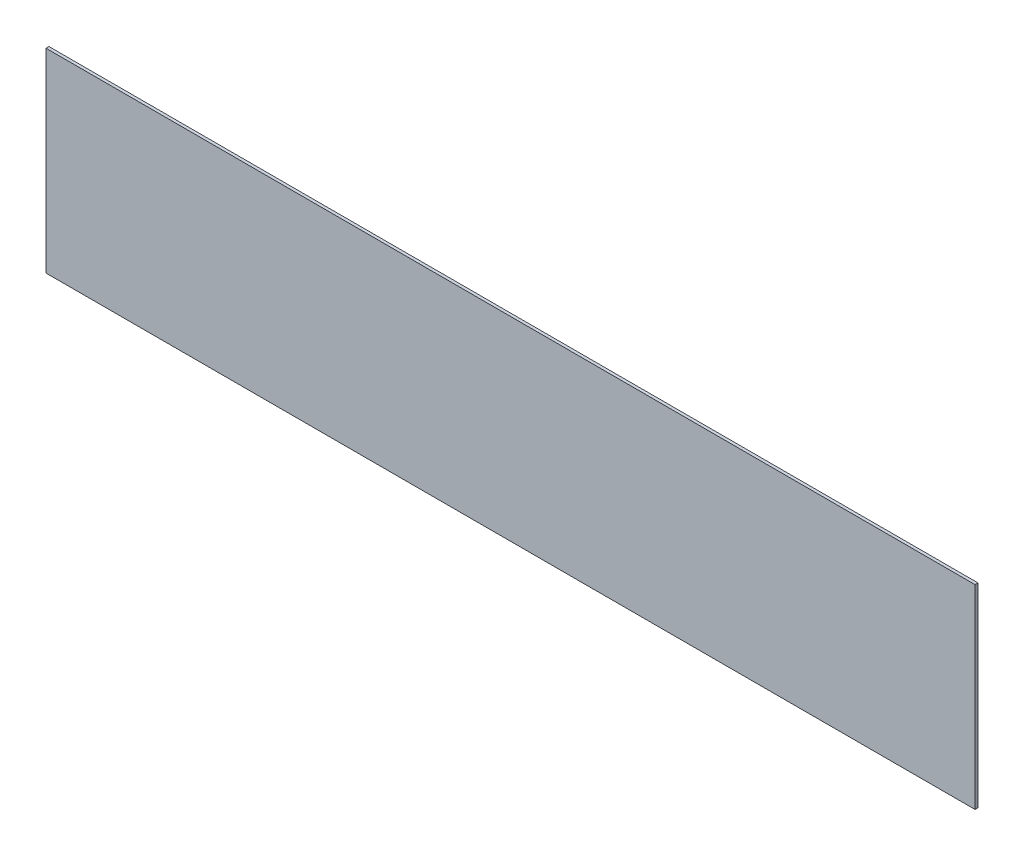
SolidWorks part; units mm, degrees
material "Pine"
ref_plane "Front Plane" through (0, 0, 0) normal (0, 0, 1) x (1, 0, 0)
ref_plane "Top Plane" through (0, 0, 0) normal (0, 1, 0) x (1, 0, 0)
ref_plane "Right Plane" through (0, 0, 0) normal (1, 0, 0) x (0, 0, -1)
sketch "Sketch2" plane through (0, 0, 0) normal (0, 0, 1) x (1, 0, 0)
  line L1 (0, 0) -> (1003.3, 0)
  line L2 (0, 0) -> (0, 210.312)
  line L3 (0, 210.312) -> (1003.3, 210.312)
  line L4 (1003.3, 0) -> (1003.3, 210.312)
  dimension "D1" = 210.312
  dimension "D2" = 1003.3
extrude "Boss-Extrude1" add sketch "Sketch2" along normal blind 3.175
